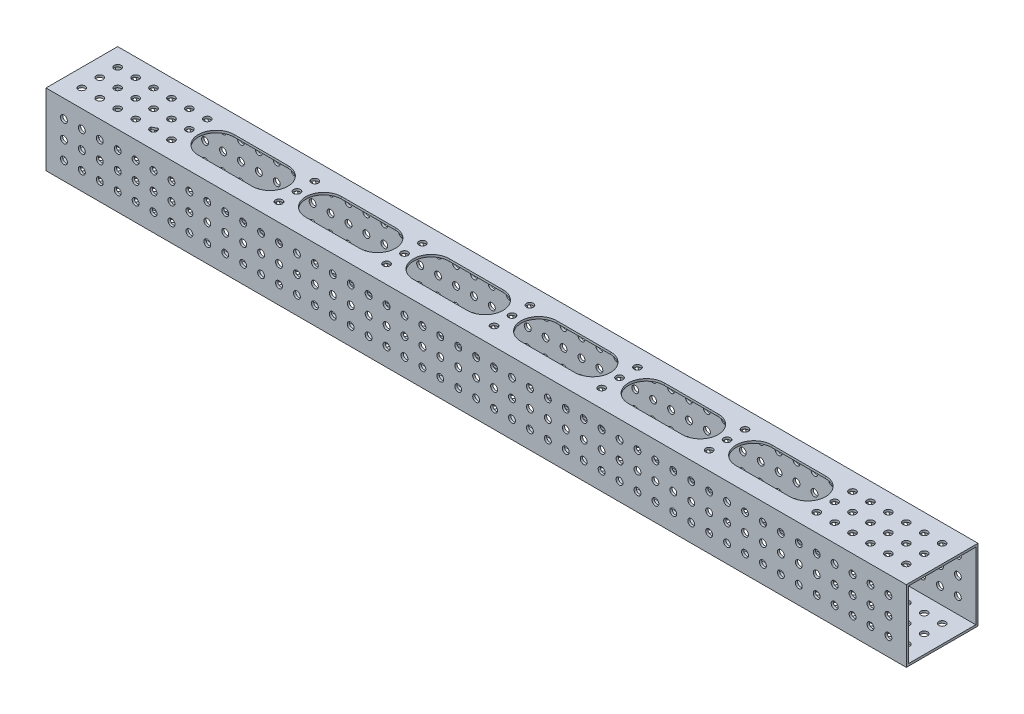
SolidWorks part; units mm, degrees
ref_plane "Front Plane" through (0, 0, 0) normal (0, 0, 1) x (1, 0, 0)
ref_plane "Top Plane" through (0, 0, 0) normal (0, 1, 0) x (1, 0, 0)
ref_plane "Right Plane" through (0, 0, 0) normal (1, 0, 0) x (0, 0, -1)
sketch "Sketch1" plane through (0, 0, 0) normal (1, 0, 0) x (0, 0, -1)
  line L1 (-25.4, -25.4) -> (25.4, -25.4)
  line L2 (-25.4, -25.4) -> (-25.4, 25.4)
  line L3 (-25.4, 25.4) -> (25.4, 25.4)
  line L4 (25.4, -25.4) -> (25.4, 25.4)
  line L5 (-25.4, -25.4) -> (25.4, 25.4) construction
  line L6 (-25.4, 25.4) -> (25.4, -25.4) construction
  line L7 (-23.8125, -23.8125) -> (23.8125, -23.8125)
  line L8 (-23.8125, -23.8125) -> (-23.8125, 23.8125)
  line L9 (-23.8125, 23.8125) -> (23.8125, 23.8125)
  line L10 (23.8125, -23.8125) -> (23.8125, 23.8125)
  line L11 (-23.8125, -23.8125) -> (23.8125, 23.8125) construction
  line L12 (-23.8125, 23.8125) -> (23.8125, -23.8125) construction
  point P0 (0, 0)
  point P7 (0, 0)
  dimension "D1" = 50.8
  dimension "D2" = 50.8
  dimension "D3" = 47.625
extrude "Boss-Extrude1" add sketch "Sketch1" along normal blind 609.6
sketch "Sketch2" plane through (0, 0, 25.4) normal (0, 0, 1) x (1, 0, 0)
  line L0 (-1000, 0) -> (49000, 0) construction
  line L2 (-994.1549, 12.7) -> (49005.8451, 12.7) construction
  line L3 (-984.8446, -12.7) -> (49015.1554, -12.7) construction
  line L4 (609.6, 25.4) -> (0, 25.4) construction
  line L5 (609.6, -25.4) -> (0, -25.4) construction
  line L6 (0, 25.4) -> (0, -25.4) construction
  line L7 (12.7, 12.7) -> (12.7, 0) construction
  line L8 (12.7, 12.7) -> (25.4, 12.7) construction
  circle A24 centre (12.7, 12.7) radius 2.4384
  circle A25 centre (12.7, 0) radius 2.4384
  circle A26 centre (12.7, -12.7) radius 2.4384
  circle A27 centre (25.4, 12.7) radius 2.4384
  circle A28 centre (25.4, 0) radius 2.4384
  circle A29 centre (25.4, -12.7) radius 2.4384
  circle A30 centre (38.1, 12.7) radius 2.4384
  circle A31 centre (38.1, 0) radius 2.4384
  circle A32 centre (38.1, -12.7) radius 2.4384
  circle A33 centre (50.8, 12.7) radius 2.4384
  circle A34 centre (50.8, 0) radius 2.4384
  circle A35 centre (50.8, -12.7) radius 2.4384
  circle A36 centre (63.5, 12.7) radius 2.4384
  circle A37 centre (63.5, 0) radius 2.4384
  circle A38 centre (63.5, -12.7) radius 2.4384
  circle A39 centre (76.2, 12.7) radius 2.4384
  circle A40 centre (76.2, 0) radius 2.4384
  circle A41 centre (76.2, -12.7) radius 2.4384
  circle A42 centre (88.9, 12.7) radius 2.4384
  circle A43 centre (88.9, 0) radius 2.4384
  circle A44 centre (88.9, -12.7) radius 2.4384
  circle A45 centre (101.6, 12.7) radius 2.4384
  circle A46 centre (101.6, 0) radius 2.4384
  circle A47 centre (101.6, -12.7) radius 2.4384
  circle A48 centre (114.3, 12.7) radius 2.4384
  circle A49 centre (114.3, 0) radius 2.4384
  circle A50 centre (114.3, -12.7) radius 2.4384
  circle A51 centre (127, 12.7) radius 2.4384
  circle A52 centre (127, 0) radius 2.4384
  circle A53 centre (127, -12.7) radius 2.4384
  circle A54 centre (139.7, 12.7) radius 2.4384
  circle A55 centre (139.7, 0) radius 2.4384
  circle A56 centre (139.7, -12.7) radius 2.4384
  circle A57 centre (152.4, 12.7) radius 2.4384
  circle A58 centre (152.4, 0) radius 2.4384
  circle A59 centre (152.4, -12.7) radius 2.4384
  circle A60 centre (165.1, 12.7) radius 2.4384
  circle A61 centre (165.1, 0) radius 2.4384
  circle A62 centre (165.1, -12.7) radius 2.4384
  circle A63 centre (177.8, 12.7) radius 2.4384
  circle A64 centre (177.8, 0) radius 2.4384
  circle A65 centre (177.8, -12.7) radius 2.4384
  circle A66 centre (190.5, 12.7) radius 2.4384
  circle A67 centre (190.5, 0) radius 2.4384
  circle A68 centre (190.5, -12.7) radius 2.4384
  circle A69 centre (203.2, 12.7) radius 2.4384
  circle A70 centre (203.2, 0) radius 2.4384
  circle A71 centre (203.2, -12.7) radius 2.4384
  circle A72 centre (215.9, 12.7) radius 2.4384
  circle A73 centre (215.9, 0) radius 2.4384
  circle A74 centre (215.9, -12.7) radius 2.4384
  circle A75 centre (228.6, 12.7) radius 2.4384
  circle A76 centre (228.6, 0) radius 2.4384
  circle A77 centre (228.6, -12.7) radius 2.4384
  circle A78 centre (241.3, 12.7) radius 2.4384
  circle A79 centre (241.3, 0) radius 2.4384
  circle A80 centre (241.3, -12.7) radius 2.4384
  circle A81 centre (254, 12.7) radius 2.4384
  circle A82 centre (254, 0) radius 2.4384
  circle A83 centre (254, -12.7) radius 2.4384
  circle A84 centre (266.7, 12.7) radius 2.4384
  circle A85 centre (266.7, 0) radius 2.4384
  circle A86 centre (266.7, -12.7) radius 2.4384
  circle A87 centre (279.4, 12.7) radius 2.4384
  circle A88 centre (279.4, 0) radius 2.4384
  circle A89 centre (279.4, -12.7) radius 2.4384
  circle A90 centre (292.1, 12.7) radius 2.4384
  circle A91 centre (292.1, 0) radius 2.4384
  circle A92 centre (292.1, -12.7) radius 2.4384
  circle A93 centre (304.8, 12.7) radius 2.4384
  circle A94 centre (304.8, 0) radius 2.4384
  circle A95 centre (304.8, -12.7) radius 2.4384
  circle A96 centre (317.5, 12.7) radius 2.4384
  circle A97 centre (317.5, 0) radius 2.4384
  circle A98 centre (317.5, -12.7) radius 2.4384
  circle A99 centre (330.2, 12.7) radius 2.4384
  circle A100 centre (330.2, 0) radius 2.4384
  circle A101 centre (330.2, -12.7) radius 2.4384
  circle A102 centre (342.9, 12.7) radius 2.4384
  circle A103 centre (342.9, 0) radius 2.4384
  circle A104 centre (342.9, -12.7) radius 2.4384
  circle A105 centre (355.6, 12.7) radius 2.4384
  circle A106 centre (355.6, 0) radius 2.4384
  circle A107 centre (355.6, -12.7) radius 2.4384
  circle A108 centre (368.3, 12.7) radius 2.4384
  circle A109 centre (368.3, 0) radius 2.4384
  circle A110 centre (368.3, -12.7) radius 2.4384
  circle A111 centre (381, 12.7) radius 2.4384
  circle A112 centre (381, 0) radius 2.4384
  circle A113 centre (381, -12.7) radius 2.4384
  circle A114 centre (393.7, 12.7) radius 2.4384
  circle A115 centre (393.7, 0) radius 2.4384
  circle A116 centre (393.7, -12.7) radius 2.4384
  circle A117 centre (406.4, 12.7) radius 2.4384
  circle A118 centre (406.4, 0) radius 2.4384
  circle A119 centre (406.4, -12.7) radius 2.4384
  circle A120 centre (419.1, 12.7) radius 2.4384
  circle A121 centre (419.1, 0) radius 2.4384
  circle A122 centre (419.1, -12.7) radius 2.4384
  circle A123 centre (431.8, 12.7) radius 2.4384
  circle A124 centre (431.8, 0) radius 2.4384
  circle A125 centre (431.8, -12.7) radius 2.4384
  circle A126 centre (444.5, 12.7) radius 2.4384
  circle A127 centre (444.5, 0) radius 2.4384
  circle A128 centre (444.5, -12.7) radius 2.4384
  circle A129 centre (457.2, 12.7) radius 2.4384
  circle A130 centre (457.2, 0) radius 2.4384
  circle A131 centre (457.2, -12.7) radius 2.4384
  circle A132 centre (469.9, 12.7) radius 2.4384
  circle A133 centre (469.9, 0) radius 2.4384
  circle A134 centre (469.9, -12.7) radius 2.4384
  circle A135 centre (482.6, 12.7) radius 2.4384
  circle A136 centre (482.6, 0) radius 2.4384
  circle A137 centre (482.6, -12.7) radius 2.4384
  circle A138 centre (495.3, 12.7) radius 2.4384
  circle A139 centre (495.3, 0) radius 2.4384
  circle A140 centre (495.3, -12.7) radius 2.4384
  circle A141 centre (508, 12.7) radius 2.4384
  circle A142 centre (508, 0) radius 2.4384
  circle A143 centre (508, -12.7) radius 2.4384
  circle A144 centre (520.7, 12.7) radius 2.4384
  circle A145 centre (520.7, 0) radius 2.4384
  circle A146 centre (520.7, -12.7) radius 2.4384
  circle A147 centre (533.4, 12.7) radius 2.4384
  circle A148 centre (533.4, 0) radius 2.4384
  circle A149 centre (533.4, -12.7) radius 2.4384
  circle A150 centre (546.1, 12.7) radius 2.4384
  circle A151 centre (546.1, 0) radius 2.4384
  circle A152 centre (546.1, -12.7) radius 2.4384
  circle A153 centre (558.8, 12.7) radius 2.4384
  circle A154 centre (558.8, 0) radius 2.4384
  circle A155 centre (558.8, -12.7) radius 2.4384
  circle A156 centre (571.5, 12.7) radius 2.4384
  circle A157 centre (571.5, 0) radius 2.4384
  circle A158 centre (571.5, -12.7) radius 2.4384
  circle A159 centre (584.2, 12.7) radius 2.4384
  circle A160 centre (584.2, 0) radius 2.4384
  circle A161 centre (584.2, -12.7) radius 2.4384
  circle A162 centre (596.9, 12.7) radius 2.4384
  circle A163 centre (596.9, 0) radius 2.4384
  circle A164 centre (596.9, -12.7) radius 2.4384
  dimension "D1" = 12.7
  dimension "D3" = 4.8768
  dimension "D2" = 12.7
  dimension "D4" = 12.7
  dimension "D6" = 12.7
  dimension "D8" = 12.7
  dimension "D5" = 3
  dimension "D7" = 47
extrude "Cut-Extrude2" cut sketch "Sketch2" against normal blind 609.6
sketch "Sketch3" plane through (0, -25.4, 0) normal (0, -1, 0) x (1, 0, 0)
  line L0 (0, 0) -> (6.35, 0)
  line L1 (76.2, 12.7) -> (63.5, 12.7) construction
  line L2 (0, 25.4) -> (0, -25.4) construction
  line L3 (19.05, 12.7) -> (57.15, 12.7)
  line L4 (19.05, -12.7) -> (57.15, -12.7)
  line L5 (609.6, 25.4) -> (0, 25.4) construction
  line L6 (95.25, 12.7) -> (133.35, 12.7)
  line L7 (95.25, -12.7) -> (133.35, -12.7)
  line L8 (171.45, 12.7) -> (209.55, 12.7)
  line L9 (171.45, -12.7) -> (209.55, -12.7)
  line L10 (247.65, 12.7) -> (285.75, 12.7)
  line L11 (247.65, -12.7) -> (285.75, -12.7)
  line L12 (323.85, 12.7) -> (361.95, 12.7)
  line L13 (323.85, -12.7) -> (361.95, -12.7)
  line L14 (400.05, 12.7) -> (438.15, 12.7)
  line L15 (400.05, -12.7) -> (438.15, -12.7)
  line L16 (476.25, 12.7) -> (514.35, 12.7)
  line L17 (476.25, -12.7) -> (514.35, -12.7)
  line L18 (552.45, 12.7) -> (590.55, 12.7)
  line L19 (552.45, -12.7) -> (590.55, -12.7)
  line L20 (535.8384, 0) -> (539.75, 0)
  line L21 (527.05, 0) -> (530.9616, 0)
  line L22 (383.4384, 0) -> (387.35, 0)
  line L23 (374.65, 0) -> (378.5616, 0)
  line L24 (459.6384, 0) -> (463.55, 0)
  line L25 (146.05, 0) -> (149.9616, 0)
  line L26 (222.25, 0) -> (226.1616, 0)
  line L27 (154.8384, 0) -> (158.75, 0)
  line L28 (307.2384, 0) -> (311.15, 0)
  line L29 (298.45, 0) -> (302.3616, 0)
  line L30 (231.0384, 0) -> (234.95, 0)
  line L31 (69.85, 0) -> (73.7616, 0)
  line L32 (78.6384, 0) -> (82.55, 0)
  line L33 (19.05, 12.7) -> (95.25, 12.7) construction
  arc A0 (19.05, 12.7) -> (19.05, -12.7) centre (19.05, 0) ccw
  arc A1 (57.15, -12.7) -> (57.15, 12.7) centre (57.15, 0) ccw
  circle A2 centre (76.2, 12.7) radius 2.4384
  circle A3 centre (76.2, 0) radius 2.4384
  circle A4 centre (76.2, -12.7) radius 2.4384
  arc A5 (95.25, 12.7) -> (95.25, -12.7) centre (95.25, 0) ccw
  arc A6 (133.35, -12.7) -> (133.35, 12.7) centre (133.35, 0) ccw
  circle A7 centre (152.4, 12.7) radius 2.4384
  circle A8 centre (152.4, 0) radius 2.4384
  circle A9 centre (152.4, -12.7) radius 2.4384
  arc A10 (171.45, 12.7) -> (171.45, -12.7) centre (171.45, 0) ccw
  arc A11 (209.55, -12.7) -> (209.55, 12.7) centre (209.55, 0) ccw
  circle A12 centre (228.6, 12.7) radius 2.4384
  circle A13 centre (228.6, 0) radius 2.4384
  circle A14 centre (228.6, -12.7) radius 2.4384
  arc A15 (247.65, 12.7) -> (247.65, -12.7) centre (247.65, 0) ccw
  arc A16 (285.75, -12.7) -> (285.75, 12.7) centre (285.75, 0) ccw
  circle A17 centre (304.8, 12.7) radius 2.4384
  circle A18 centre (304.8, 0) radius 2.4384
  circle A19 centre (304.8, -12.7) radius 2.4384
  arc A20 (323.85, 12.7) -> (323.85, -12.7) centre (323.85, 0) ccw
  arc A21 (361.95, -12.7) -> (361.95, 12.7) centre (361.95, 0) ccw
  circle A22 centre (381, 12.7) radius 2.4384
  circle A23 centre (381, 0) radius 2.4384
  circle A24 centre (381, -12.7) radius 2.4384
  arc A25 (400.05, 12.7) -> (400.05, -12.7) centre (400.05, 0) ccw
  arc A26 (438.15, -12.7) -> (438.15, 12.7) centre (438.15, 0) ccw
  circle A27 centre (457.2, 12.7) radius 2.4384
  circle A28 centre (457.2, 0) radius 2.4384
  circle A29 centre (457.2, -12.7) radius 2.4384
  arc A30 (476.25, 12.7) -> (476.25, -12.7) centre (476.25, 0) ccw
  arc A31 (514.35, -12.7) -> (514.35, 12.7) centre (514.35, 0) ccw
  circle A32 centre (533.4, 12.7) radius 2.4384
  circle A33 centre (533.4, 0) radius 2.4384
  circle A34 centre (533.4, -12.7) radius 2.4384
  arc A35 (552.45, 12.7) -> (552.45, -12.7) centre (552.45, 0) ccw
  arc A36 (590.55, -12.7) -> (590.55, 12.7) centre (590.55, 0) ccw
  circle A40 centre (609.6, 12.7) radius 2.4384 [skipped]
  circle A41 centre (609.6, 0) radius 2.4384 [skipped]
  circle A42 centre (609.6, -12.7) radius 2.4384 [skipped]
  circle A43 centre (546.1, 12.7) radius 2.4384
  circle A44 centre (546.1, 0) radius 2.4384
  circle A45 centre (546.1, -12.7) radius 2.4384
  circle A46 centre (558.8, 12.7) radius 2.4384
  circle A47 centre (558.8, 0) radius 2.4384
  circle A48 centre (558.8, -12.7) radius 2.4384
  circle A49 centre (571.5, 12.7) radius 2.4384
  circle A50 centre (571.5, 0) radius 2.4384
  circle A51 centre (571.5, -12.7) radius 2.4384
  circle A52 centre (584.2, 12.7) radius 2.4384
  circle A53 centre (584.2, 0) radius 2.4384
  circle A54 centre (584.2, -12.7) radius 2.4384
  circle A55 centre (596.9, 12.7) radius 2.4384
  circle A56 centre (596.9, 0) radius 2.4384
  circle A57 centre (596.9, -12.7) radius 2.4384
  circle A58 centre (63.5, 12.7) radius 2.4384
  circle A59 centre (63.5, -12.7) radius 2.4384
  circle A60 centre (63.5, 0) radius 2.4384
  circle A61 centre (50.8, 12.7) radius 2.4384
  circle A62 centre (50.8, -12.7) radius 2.4384
  circle A63 centre (50.8, 0) radius 2.4384
  circle A64 centre (38.1, 12.7) radius 2.4384
  circle A65 centre (38.1, -12.7) radius 2.4384
  circle A66 centre (38.1, 0) radius 2.4384
  circle A67 centre (25.4, 12.7) radius 2.4384
  circle A68 centre (25.4, -12.7) radius 2.4384
  circle A69 centre (25.4, 0) radius 2.4384
  circle A70 centre (12.7, 12.7) radius 2.4384
  circle A71 centre (12.7, -12.7) radius 2.4384
  circle A72 centre (12.7, 0) radius 2.4384
  dimension "D1" = 25.4
  dimension "D2" = 19.05
  dimension "D3" = 25.4
  dimension "D4" = 38.1
  dimension "D5" = 4.8768
  dimension ".2" = 4.8768
  dimension "D6" = 4.8768
  dimension "D8" = 12.7
  dimension "D9" = 12.7
  dimension "D10" = 76.2
  dimension "D11" = 76.2
  dimension "D12" = 76.2
  dimension "D7" = 12.7
  dimension "D15" = 76.2
  dimension "D16" = 6
  dimension "D17" = 12.7
  dimension "D18" = 12.7
  dimension "D13" = 8
  dimension "D14" = 6
extrude "Cut-Extrude3" cut sketch "Sketch3" against normal blind 76.2 contours L7 A6 L6 A5 | L9 A11 L8 A10 | L11 A16 L10 A15 | L13 A21 L12 A20 | A4 | A8 | A9 | A7 | A18 | A23 | L15 A26 L14 A25 | A28 | L17 A31 L16 A30 | A63 | A66 | A69 | A1 A58 | A2 | A3 | A12 | A13 | A14 | A17 | A19 | A22 | A24 | A27 | A29 | A33 | A32 | A34 | A62 | A61 | A64 | A65 | A68 | A67 | A70 | A72 | A71 | A60 | A59 | A45 | A48 | A51 | A44 | A43 | A46 | A49 | A52 | A53 | A50 | A47 | A54 | A57 | A56 | A55 region at (419.1, -25.4, 0) region at (381, -25.4, 0) region at (342.9, -25.4, 0) region at (304.8, -25.4, 0) region at (266.7, -25.4, 0) region at (190.5, -25.4, 0) region at (152.4, -25.4, 0) region at (114.3, -25.4, 0) region at (63.6226, -25.4, 12.9453) region at (457.2, -25.4, 0) region at (495.3, -25.4, 0) region at (76.2, -25.4, -12.7) region at (152.4, -25.4, 12.7) region at (152.4, -25.4, -12.7) region at (50.8, -25.4, 0) region at (38.1, -25.4, 0) region at (25.4, -25.4, 0)
